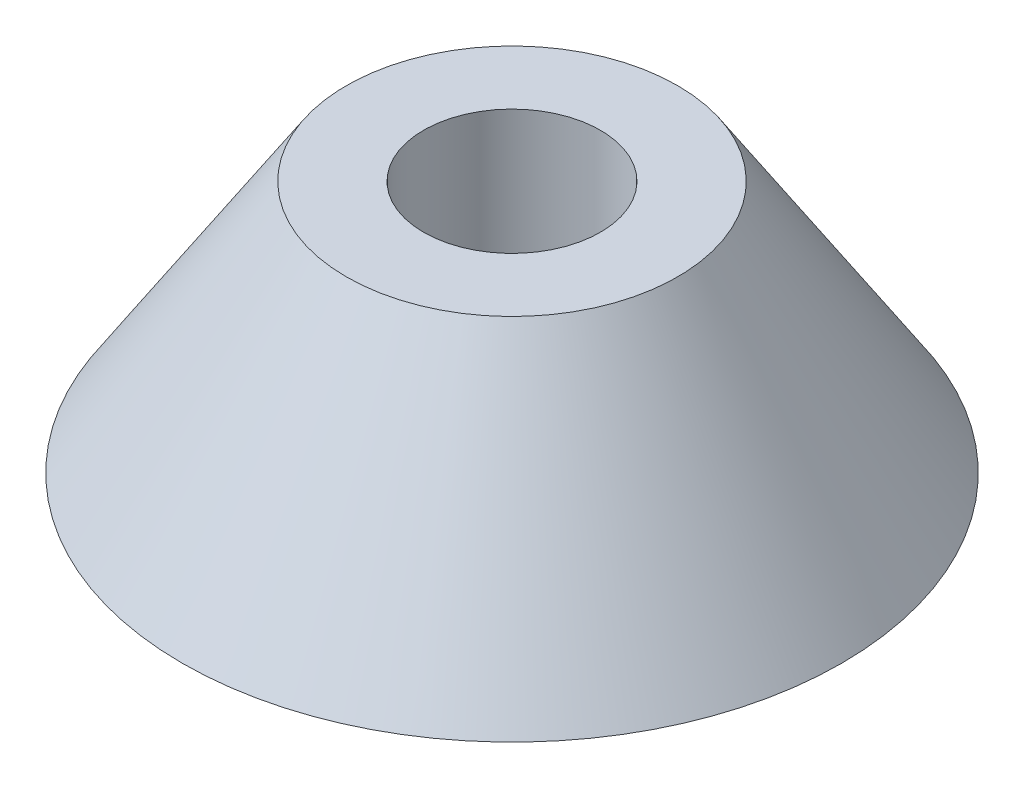
SolidWorks part; units mm, degrees
ref_plane "Front Plane" through (0, 0, 0) normal (0, 0, 1) x (1, 0, 0)
ref_plane "Top Plane" through (0, 0, 0) normal (0, 1, 0) x (1, 0, 0)
ref_plane "Right Plane" through (0, 0, 0) normal (1, 0, 0) x (0, 0, -1)
sketch "Sketch1" plane through (0, 0, 0) normal (0, 1, 0) x (1, 0, 0)
  circle A0 centre (0, 0) radius 7.5
  circle A1 centre (0, 0) radius 1.75
  dimension "D1" = 15
  dimension "D2" = 3.5
extrude "Boss-Extrude1" add sketch "Sketch1" along normal blind 5
chamfer "Chamfer1" distance 6.5 angle 33 1 edges at (0, 5, 7.5) first distance on face at (0, 5, 7.5)
